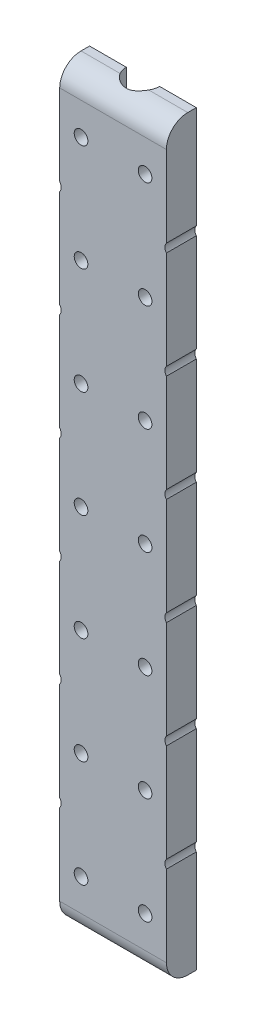
SolidWorks part; units mm, degrees
ref_plane "前视基准面" through (0, 0, 0) normal (0, 0, 1) x (1, 0, 0)
ref_plane "上视基准面" through (0, 0, 0) normal (0, 1, 0) x (1, 0, 0)
ref_plane "右视基准面" through (0, 0, 0) normal (1, 0, 0) x (0, 0, -1)
other "Configuration Table"
sketch "草图2" plane through (0, 0, 0) normal (0, 1, 0) x (1, 0, 0)
  line L0 (-3.9, 0) -> (-12.5, 0)
  line L1 (-12.5, 0) -> (-12.5, -7)
  line L2 (-12.5, -7) -> (12.5, -7)
  line L3 (12.5, -7) -> (12.5, 0)
  line L4 (12.5, 0) -> (3.9, 0)
  arc A0 (-3.9, 0) -> (3.9, 0) centre (0, 0) ccw
  dimension "D1" = 3.9
  dimension "D2" = 25
  dimension "D3" = 7
extrude "凸台-拉伸1" add sketch "草图2" along normal mid plane 175
sketch "草图4" plane through (0, 0, 0) normal (0, 0, 1) x (1, 0, 0)
  line L0 (0, 87.5) -> (0, 81.5829) construction
  line L2 (13.75, 62.5) -> (-13.75, 62.5) construction
  circle A0 centre (-13.75, 62.5) radius 1.6
  circle A1 centre (13.75, 62.5) radius 1.6
  point P8 (0, 62.5)
  dimension "D1" = 3.2
  dimension "D3" = 27.5
extrude "切除-拉伸3" cut sketch "草图4" along normal through all
pattern_linear "阵列(线性)2" count 6 spacing 25 along (0, -1, 0) of "切除-拉伸3"
fillet "圆角1" radius 5 2 edges at (0, -87.5, 7) (0, 87.5, 7)
sketch "草图5" plane through (0, 0, 7) normal (0, 0, 1) x (1, 0, 0)
  line L0 (-12.5, 87.5) -> (-3.3481, 87.5) construction
  line L1 (-12.5, 82.5) -> (-12.5, 63.4987) construction
  circle A0 centre (-7.5, 75) radius 1.6
  dimension "D1" = 3.2
  dimension "D2" = 12.5
  dimension "D3" = 5
extrude "切除-拉伸4" cut sketch "草图5" against normal through all
pattern_linear "阵列(线性)3" count 2 spacing 15 along (1, 0, 0) count 7 spacing 25 along (0, -1, 0) of "切除-拉伸4"
